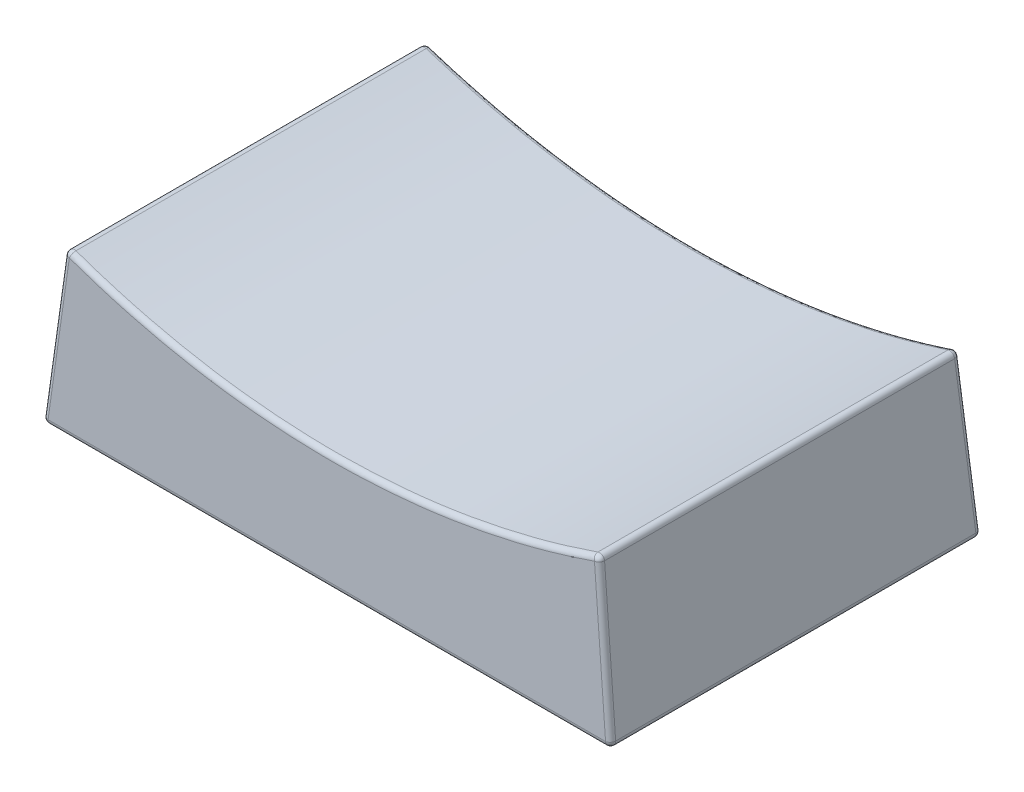
SolidWorks part; units mm, degrees
material "NEOPRENE"
ref_plane "Front Plane" through (0, 0, 0) normal (0, 0, 1) x (1, 0, 0)
ref_plane "Top Plane" through (0, 0, 0) normal (0, 1, 0) x (1, 0, 0)
ref_plane "Right Plane" through (0, 0, 0) normal (1, 0, 0) x (0, 0, -1)
sketch "Profile" plane through (0, 0, 0) normal (0, 0, 1) x (1, 0, 0)
  line L3 (-14, 0) -> (14, 0)
  line L4 (-13.5, 4.5) -> (13.5, 4.5) construction
  line L5 (-14, 0) -> (-13.1389, 7.75)
  line L6 (14, 0) -> (13.1389, 7.75)
  arc A1 (-13.1389, 7.75) -> (13.1389, 7.75) centre (0, 45.5305) ccw
  point P3 (0, 0)
  point P6 (0, 4.5)
  dimension "D1" = 28
  dimension "D3" = 27
  dimension "D4" = 7.75
  dimension "D5" = 40
  dimension "D2" = 4.5
extrude "Body" add sketch "Profile" along normal mid plane 18.25
draft "Draft Sides" type of draft neutral plane draft angle 2 neutral plane "Top Plane" faces to draft 2 face at (0, 3.3201, -9.125) face at (0, 3.3201, 9.125) neutral plane through (0, 0, 0) neutral plane normal (0, 1, 0) parameters "D1"=2
sketch "Top Cut Out Sketch" plane through (0, 0, 0) normal (0, 1, 0) x (1, 0, 0)
  circle A0 centre (0, 0) radius 5
  dimension "D1" = 10
extrude "Top Cut Out" cut sketch "Top Cut Out Sketch" along normal blind 1.75
fillet "Fillet Edges" radius 0.25 14 edges at (0, 1.75, 5) (-14, 0, 0) (0, 0, 9.125) (14, 0, 0) (0, 0, -9.125) (0, 0, 5) (13.1389, 7.75, 0) (0, 5.5305, 8.9319) (-13.1389, 7.75, 0) (0, 5.5305, -8.9319) (13.5694, 3.875, 8.9897) (13.5694, 3.875, -8.9897) (-13.5694, 3.875, -8.9897) (-13.5694, 3.875, 8.9897)
